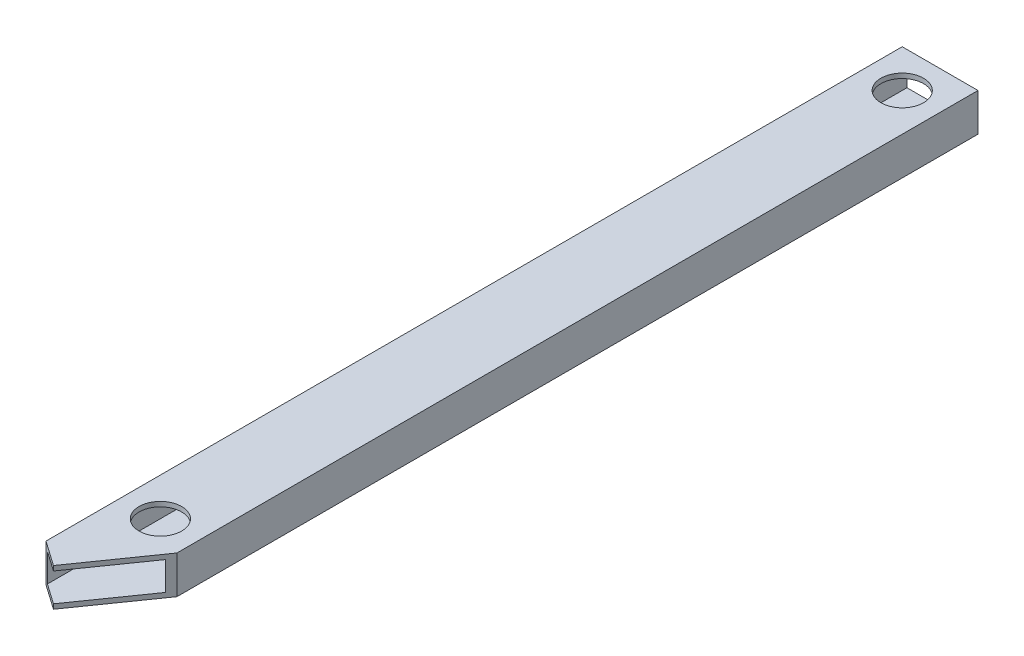
SolidWorks part; units mm, degrees
ref_plane "Front Plane" through (0, 0, 0) normal (0, 0, 1) x (1, 0, 0)
ref_plane "Top Plane" through (0, 0, 0) normal (0, 1, 0) x (1, 0, 0)
ref_plane "Right Plane" through (0, 0, 0) normal (1, 0, 0) x (0, 0, -1)
sketch "Sketch1" plane through (0, 0, 0) normal (0, 0, 1) x (1, 0, 0)
  line L1 (0, 0) -> (50.8, 0)
  line L2 (0, 0) -> (0, 25.4)
  line L3 (0, 25.4) -> (50.8, 25.4)
  line L4 (50.8, 0) -> (50.8, 25.4)
extrude "Boss-Extrude1" add sketch "Sketch1" along normal blind 609.6
sketch "Sketch2" plane through (0, 0, 0) normal (0, 0, -1) x (-1, 0, 0)
  line L1 (-3.175, 3.175) -> (-47.625, 3.175)
  line L2 (-3.175, 3.175) -> (-3.175, 22.225)
  line L3 (-3.175, 22.225) -> (-47.625, 22.225)
  line L4 (-47.625, 3.175) -> (-47.625, 22.225)
extrude "Cut-Extrude1" cut sketch "Sketch2" against normal blind 609.6
sketch "Sketch4" plane through (0, 0, 0) normal (0, -1, 0) x (1, 0, 0)
  line L2 (0, 574.0295) -> (16.7127, 585.7318)
  line L7 (16.7127, 585.7318) -> (50.8, 537.0501)
  line L13 (50.8, 609.6) -> (50.8, 0) construction
  line L14 (50.8, 537.0501) -> (50.8, 609.6)
  line L15 (50.8, 609.6) -> (0, 609.6)
  line L17 (0, 609.6) -> (0, 0) construction
  line L18 (0, 574.0295) -> (0, 609.6)
  dimension "D1" = 35
extrude "Cut-Extrude3" cut sketch "Sketch4" against normal blind 25.4
sketch "Sketch6" plane through (0, 25.4, 0) normal (0, 1, 0) x (1, 0, 0)
  line L0 (25.4, 0) -> (25.4, -25.4) construction
  line L1 (50.8, 0) -> (0, 0) construction
  circle A0 centre (25.4, -25.4) radius 14.2875
extrude "Cut-Extrude5" cut sketch "Sketch6" against normal blind 3.175
sketch "Sketch8" plane through (0, 25.4, 0) normal (0, 1, 0) x (1, 0, 0)
  line L0 (50.8, -537.0501) -> (0, -537.0501) construction
  line L1 (0, -574.0295) -> (0, 0) construction
  line L2 (25.4, -537.0501) -> (25.4, -508.4751) construction
  circle A0 centre (25.4, -522.7626) radius 14.2875
extrude "Cut-Extrude7" cut sketch "Sketch8" against normal blind 3.175
